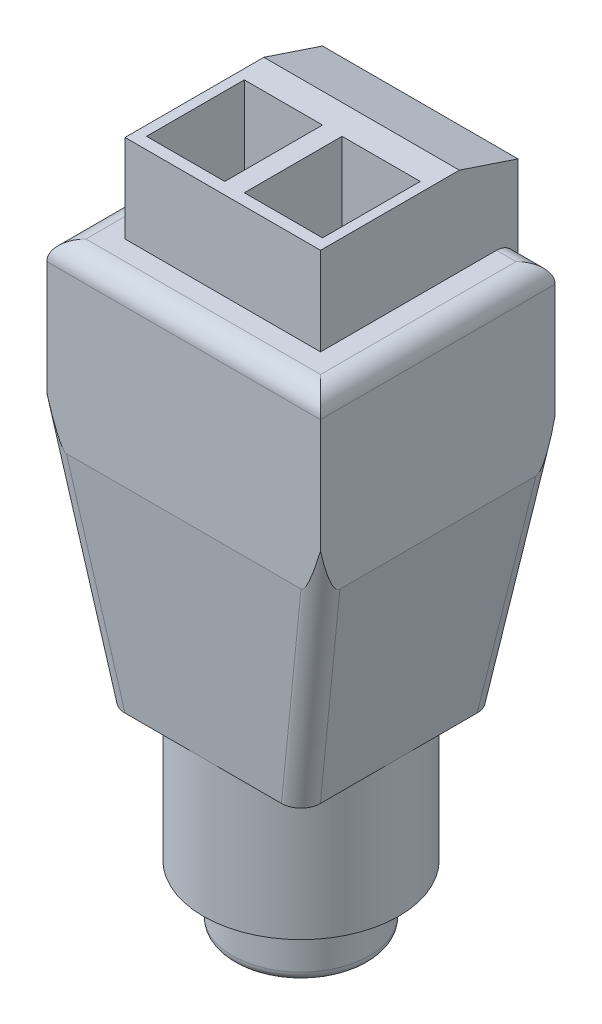
SolidWorks part; units mm, degrees
ref_plane "Front" through (0, 0, 0) normal (0, 0, 1) x (1, 0, 0)
ref_plane "Top" through (0, 0, 0) normal (0, 1, 0) x (1, 0, 0)
ref_plane "Right" through (0, 0, 0) normal (1, 0, 0) x (0, 0, -1)
sketch "草图1" plane through (0, 0, 0) normal (0, 1, 0) x (1, 0, 0)
  line L1 (0, 0) -> (14, 0)
  line L2 (0, 0) -> (0, 12)
  line L3 (0, 12) -> (14, 12)
  line L4 (14, 0) -> (14, 12)
  dimension "D1" = 14
  dimension "D2" = 12
extrude "凸台-拉伸1" add sketch "草图1" along normal blind 9
fillet "圆角2" radius 1 4 edges at (7, 9, -12) (14, 9, -6) (7, 9, 0) (0, 9, -6)
sketch "草图4" plane through (0, 0, 0) normal (0, -1, 0) x (1, 0, 0)
  line L1 (0, 0) -> (14, 0)
  line L2 (0, 0) -> (0, -12)
  line L3 (0, -12) -> (14, -12)
  line L4 (14, 0) -> (14, -12)
ref_plane "基准面2" through (0, -11, 0) normal (0, -1, 0) x (-1, 0, 0)
sketch "草图5" plane through (0, -11, 0) normal (0, -1, 0) x (-1, 0, 0)
  line L0 (0, 0) -> (-14, 0) construction
  line L1 (-2, 1) -> (-12, 1)
  line L2 (-2, 1) -> (-2, 11)
  line L3 (-2, 11) -> (-12, 11)
  line L4 (-12, 1) -> (-12, 11)
  line L5 (-14, 0) -> (-14, 12) construction
  dimension "D1" = 10
  dimension "D2" = 10
  dimension "D3" = 1
  dimension "D4" = 2
loft "放样1" add profiles "草图4", "草图5"
fillet "圆角3" radius 1 4 edges
sketch "草图6" plane through (0, -11, 0) normal (0, -1, 0) x (1, 0, 0)
  circle A0 centre (7, -6) radius 2.5
sketch "草图8" plane through (0, 0, -12) normal (0, 0, -1) x (-1, 0, 0)
  line L0 (-13, 9) -> (-1, 9) construction
  line L1 (-2, 7.5) -> (-12, 7.5)
  line L2 (-2, 7.5) -> (-2, 13.1076)
  line L3 (-2, 13.1076) -> (-12, 13.1076)
  line L4 (-12, 7.5) -> (-12, 13.1076)
  point P6 (-7, 7.5)
  point P7 (-7, 9)
  dimension "D1" = 10
  dimension "D2" = 1.5
  dimension "D3" = 0
extrude "切除-拉伸2" cut sketch "草图8" against normal blind 10
sketch "草图9" plane through (0, 0, -2) normal (0, 0, -1) x (-1, 0, 0)
  line L1 (-12, 7.5) -> (-2, 7.5)
  line L2 (-12, 7.5) -> (-12, 13.5)
  line L3 (-12, 13.5) -> (-2, 13.5)
  line L4 (-2, 7.5) -> (-2, 13.5)
  dimension "D1" = 6
extrude "凸台-拉伸3" add sketch "草图9" along normal blind 10.1
sketch "草图10" plane through (0, 0, -12.1) normal (0, 0, -1) x (-1, 0, 0)
  line L0 (-2, 7.5) -> (-2, 13.5) construction
  line L1 (-12, 13.5) -> (-12, 7.5) construction
  line L2 (-12, 7.5) -> (-2, 7.5) construction
  line L3 (-12, 7.5) -> (-2, 7.5) construction
  circle A0 centre (-4.5, 10) radius 1.75
  circle A1 centre (-9.5, 10) radius 1.75
  dimension "D1" = 2.5
  dimension "D2" = 2.5
  dimension "D3" = 2.5
  dimension "D4" = 2.5
extrude "切除-拉伸3" cut sketch "草图10" against normal blind 0.5
sketch "草图11" plane through (2, 0, 0) normal (-1, 0, 0) x (0, 0, 1)
  line L0 (-12.1, 12.5) -> (-12.1, 13.5)
  line L1 (-12.1, 7.5) -> (-12.1, 13.5) construction
  line L2 (-12.1, 13.5) -> (-9.1, 13.5)
  line L3 (-12.1, 13.5) -> (-2, 13.5) construction
  line L4 (-9.1, 13.5) -> (-12.1, 12.5)
  dimension "D1" = 1
  dimension "D2" = 3
extrude "切除-拉伸4" cut sketch "草图11" against normal through all
sketch "草图12" plane through (0, 13.5, 0) normal (0, 1, 0) x (1, 0, 0)
  line L0 (2, 2) -> (2, 11) construction
  line L1 (2.5, 7.6) -> (6.5, 7.6)
  line L2 (2.5, 7.6) -> (2.5, 2.6)
  line L3 (2.5, 2.6) -> (6.5, 2.6)
  line L4 (6.5, 7.6) -> (6.5, 2.6)
  line L5 (2, 2) -> (12, 2) construction
  line L6 (12, 9.1) -> (12, 2) construction
  line L7 (7.5, 7.6) -> (11.5, 7.6)
  line L8 (7.5, 7.6) -> (7.5, 2.6)
  line L9 (7.5, 2.6) -> (11.5, 2.6)
  line L10 (11.5, 7.6) -> (11.5, 2.6)
  dimension "D1" = 4
  dimension "D2" = 5
  dimension "D3" = 0.5
  dimension "D4" = 0.6
  dimension "D5" = 4
  dimension "D6" = 0.5
extrude "切除-拉伸5" cut sketch "草图12" against normal blind 5
sketch "草图14" plane through (0, -11, 0) normal (0, -1, 0) x (1, 0, 0)
  circle A0 centre (7, -6) radius 3.5
  circle A1 centre (7, -6) radius 3
sketch "草图15" plane through (0, -11, 0) normal (0, -1, 0) x (1, 0, 0)
  line L0 (6.95, -5.2517) -> (6.95, -6.7483)
  line L1 (7.05, -5.2517) -> (7.05, -6.7483)
  arc A0 (7.05, -6.7483) -> (7.05, -5.2517) centre (7, -6) ccw
  arc A1 (6.95, -5.2517) -> (6.95, -6.7483) centre (7, -6) ccw
  dimension "D1" = 0.05
  dimension "D3" = 1.5
  dimension "D2" = 0.05
extrude "凸台-拉伸5" add sketch "草图15" along normal blind 3
sketch "草图17" plane through (0, -11, 0) normal (0, -1, 0) x (1, 0, 0)
  circle A0 centre (7, -6) radius 5
extrude "凸台-拉伸6" add sketch "草图17" along normal blind 7
extrude "凸台-拉伸7" add sketch "草图14" along normal blind 10
fillet "圆角5" radius 0.5 1 edges at (7, -21, -9.5)
sketch "草图18" plane through (0, -18, 0) normal (0, -1, 0) x (1, 0, 0)
  line L0 (6.3577, -5.9) -> (7.6423, -5.9)
  line L1 (6.3577, -6.1) -> (7.6423, -6.1)
  circle A0 centre (7, -6) radius 3
  arc A3 (6.3577, -6.1) -> (7.6423, -6.1) centre (7, -6) ccw
  arc A4 (7.6423, -5.9) -> (6.3577, -5.9) centre (7, -6) ccw
extrude "切除-拉伸7" cut sketch "草图18" against normal blind 5
fillet "圆角6" radius 0.5 2 edges at (7, -18, -6.65) (7, -18, -5.35)
